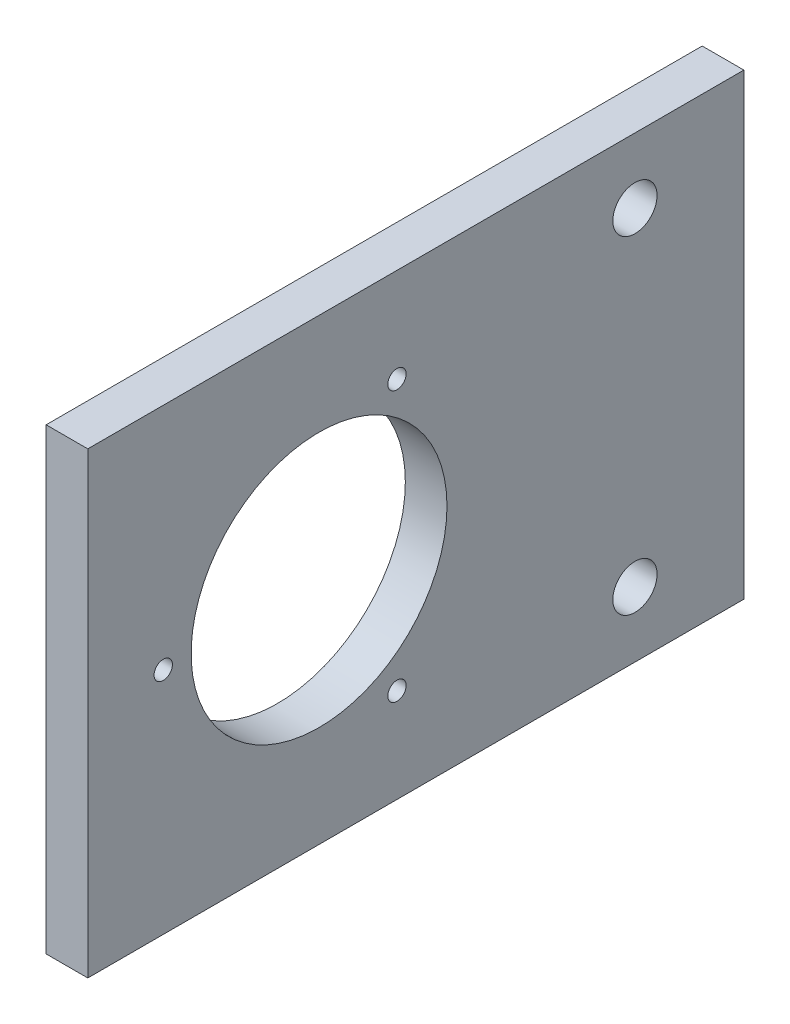
SolidWorks part; units mm, degrees
ref_plane "Front Plane" through (0, 0, 0) normal (1, 0, 0) x (0, 1, 0)
ref_plane "Top Plane" through (0, 0, 0) normal (0, 0, 1) x (0, 1, 0)
ref_plane "Right Plane" through (0, 0, 0) normal (0, 1, 0) x (-1, 0, 0)
sketch "Sketch1" plane through (0, 0, 0) normal (1, 0, 0) x (0, 1, 0)
  line L0 (0, 50) -> (0, -50) construction
  line L1 (-34.925, -50) -> (34.925, -50)
  line L2 (-34.925, -50) -> (-34.925, 50)
  line L3 (-34.925, 50) -> (34.925, 50)
  line L4 (34.925, -50) -> (34.925, 50)
  line L5 (-34.925, -50) -> (34.925, 50) construction
  line L6 (-34.925, 50) -> (34.925, -50) construction
  line L7 (-34.925, 14.75) -> (34.925, 14.75) construction
  line L8 (0, 14.75) -> (0, 38.5) construction
  line L9 (-25, -33.4) -> (25, -33.4) construction
  line L10 (-25, -33.4) -> (-25, 33.4) construction
  line L11 (-25, 33.4) -> (25, 33.4) construction
  line L12 (25, -33.4) -> (25, 33.4) construction
  line L13 (-25, -33.4) -> (25, 33.4) construction
  line L14 (-25, 33.4) -> (25, -33.4) construction
  line L15 (0, 14.75) -> (-20.5681, 2.875) construction
  line L16 (0, 14.75) -> (20.5681, 2.875) construction
  circle A5 centre (0, 14.75) radius 19.5
  circle A6 centre (-25, -33.4) radius 3.3731
  circle A7 centre (25, -33.4) radius 3.3731
  circle A8 centre (0, 38.5) radius 1.4
  circle A9 centre (20.5681, 2.875) radius 1.4
  circle A10 centre (-20.5681, 2.875) radius 1.4
  point P0 (0, 0)
  point P16 (-21.9236, 2.0924)
  point P20 (0, 0)
  dimension "D5" = 120
  dimension "D6" = 2.8
  dimension "D7" = 23.75
  dimension "D8" = 39
  dimension "D11" = 23.75
  dimension "D12" = 6.7462
  dimension "D4" = 120
  dimension "D1" = 69.85
  dimension "D2" = 100
  dimension "D3" = 64.75
  dimension "D9" = 16.6
  dimension "D10" = 50
extrude "Boss-Extrude1" add sketch "Sketch1" along normal blind 6.35
